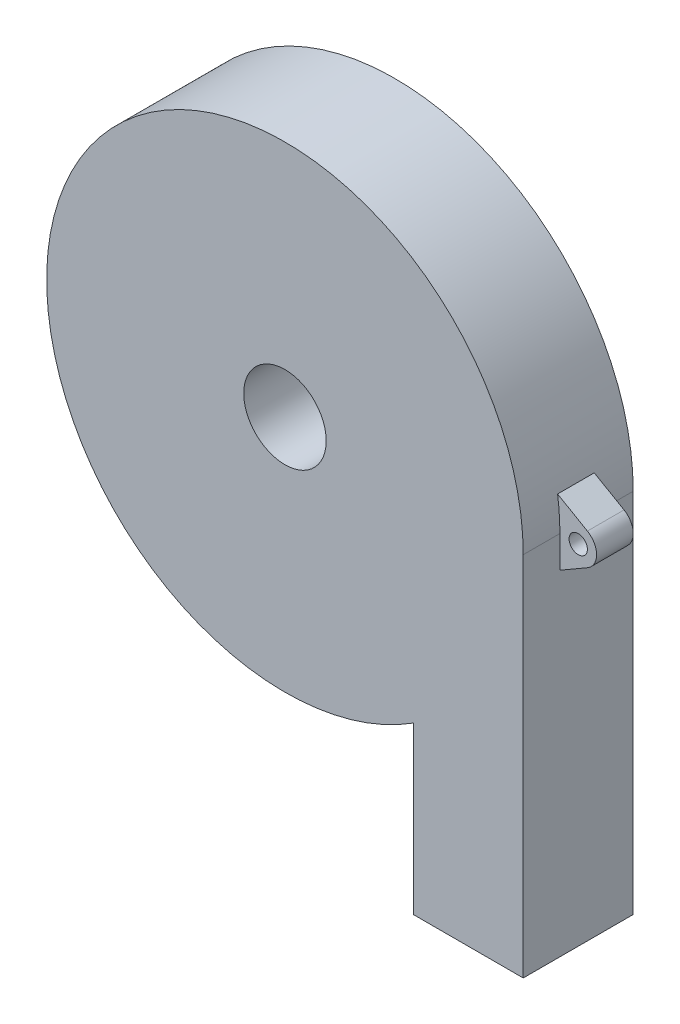
SolidWorks part; units mm, degrees
ref_plane "Front Plane" through (0, 0, 0) normal (0, 0, 1) x (1, 0, 0)
ref_plane "Top Plane" through (0, 0, 0) normal (0, 1, 0) x (1, 0, 0)
ref_plane "Right Plane" through (0, 0, 0) normal (1, 0, 0) x (0, 0, -1)
sketch "Sketch2" plane through (0, 0, 0) normal (0, 0, 1) x (1, 0, 0)
  line L0 (13, 0) -> (13, -20)
  line L1 (13, -20) -> (7, -20)
  line L2 (7, -20) -> (7, -10.9545)
  line L3 (10, 0) -> (10, -20) construction
  arc A0 (13, 0) -> (7, -10.9545) centre (0, 0) ccw
  circle A1 centre (0, 0) radius 10 construction
  dimension "D1" = 20
  dimension "D2" = 6
  dimension "D3" = 20
extrude "Boss-Extrude1" add sketch "Sketch2" along normal mid plane 6
hole_wizard "M4 Clearance Hole1" positions "Sketch3" profile "Sketch4" hole size "M4" standard "ANSI Metric" end condition up to next
sketch "Sketch3" plane through (0, 0, 3) normal (0, 0, 1) x (1, 0, 0)
  point P2 (0, 0)
sketch "Sketch4" plane through (0, 0, 3) normal (1, 0, 0) x (0, -1, 0)
  line L0 (0, 0) -> (0, 6)
  line L1 (0, 6) -> (2.25, 6)
  line L2 (2.25, 6) -> (2.25, 0)
  line L5 (2.25, 0) -> (0, 0)
  line L11 (0, -6.35) -> (0, 107.95) construction
  dimension "Thru Hole Dia." = 4.5
  dimension "Thru Hole Depth" = 6
sketch "Sketch5" plane through (0, -20, 0) normal (0, -1, 0) x (1, 0, 0)
  line L0 (13, 3) -> (7, -3) construction
  circle A0 centre (10, 0) radius 1.5875
  dimension "D1" = 3.175
extrude "Cut-Extrude1" cut sketch "Sketch5" against normal blind 20
ref_axis "Axis1" through (10, 0, 0) along (0, -1, 0)
sketch "Sketch6" plane through (0, 0, 0) normal (0, 0, 1) x (1, 0, 0)
  line L0 (13, -20) -> (13, 0) construction
  line L1 (13, -1.7321) -> (13, 0)
  line L2 (13, -1.7321) -> (14.5, -0.866)
  line L3 (14.5, 0.866) -> (12.8741, 1.8047)
  arc A0 (13, 0) -> (7, -10.9545) centre (0, 0) ccw construction
  arc A1 (13, 0) -> (12.8741, 1.8047) centre (0, 0) ccw
  arc A2 (14.5, -0.866) -> (14.5, 0.866) centre (14, 0) ccw
  dimension "D1" = 1
  dimension "D2" = 60
extrude "Boss-Extrude2" add sketch "Sketch6" along normal mid plane 2
sketch "Sketch7" plane through (0, 0, 1) normal (0, 0, 1) x (1, 0, 0)
  circle A0 centre (14, 0) radius 0.5
  arc A1 (14.5, -0.866) -> (14.5, 0.866) centre (14, 0) ccw construction
  dimension "D1" = 1
extrude "Cut-Extrude2" cut sketch "Sketch7" against normal through all both and the other way through all
